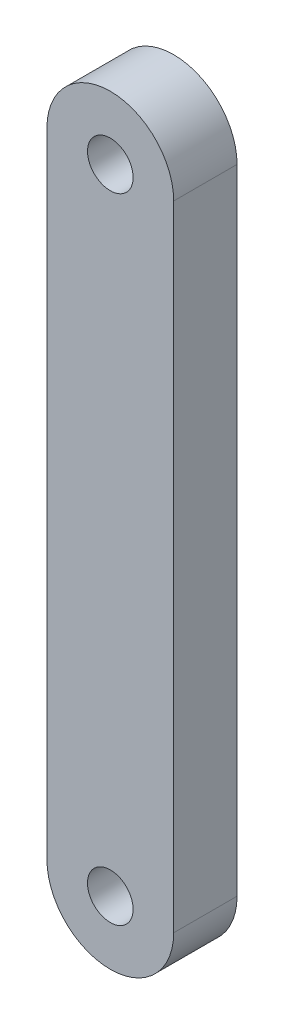
SolidWorks part; units mm, degrees
ref_plane "Front Plane" through (0, 0, 0) normal (0, 0, 1) x (1, 0, 0)
ref_plane "Top Plane" through (0, 0, 0) normal (0, 1, 0) x (1, 0, 0)
ref_plane "Right Plane" through (0, 0, 0) normal (1, 0, 0) x (0, 0, -1)
sketch "Sketch1" plane through (0, 0, 0) normal (0, 0, 1) x (1, 0, 0)
  line L0 (0, 25) -> (0, -25) construction
  line L1 (5, 25) -> (5, -25)
  line L2 (-5, 25) -> (-5, -25)
  arc A0 (5, 25) -> (-5, 25) centre (0, 25) ccw
  arc A1 (-5, -25) -> (5, -25) centre (0, -25) ccw
  point P3 (0, 0)
  dimension "D1" = 10
  dimension "D2" = 50
extrude "Boss-Extrude1" add sketch "Sketch1" along normal blind 5
hole_wizard "M3 Clearance Hole1" positions "Sketch2" profile "Sketch3" hole size "M3" standard "ANSI Metric" end condition through all
sketch "Sketch2" plane through (0, 0, 5) normal (0, 0, 1) x (1, 0, 0)
  arc A0 (-5, -25) -> (5, -25) centre (0, -25) ccw construction
  arc A1 (5, 25) -> (-5, 25) centre (0, 25) ccw construction
  point P0 (0, 25)
  point P2 (0, -25)
sketch "Sketch3" plane through (0, 25, 5) normal (1, 0, 0) x (0, -1, 0)
  line L0 (0, 0) -> (0, 5)
  line L1 (0, 5) -> (1.8, 5)
  line L2 (1.8, 5) -> (1.8, 0)
  line L5 (1.8, 0) -> (0, 0)
  line L11 (0, -6.35) -> (0, 107.95) construction
  dimension "Thru Hole Dia." = 3.6
  dimension "Thru Hole Depth" = 5
